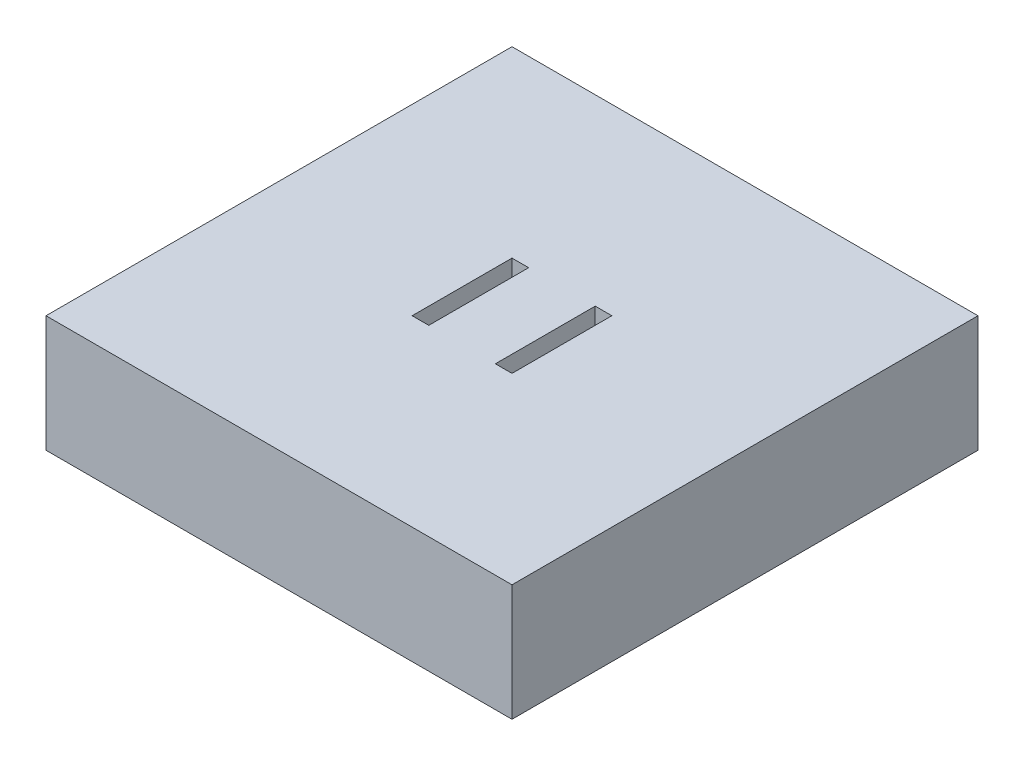
SolidWorks part; units mm, degrees
ref_plane "Front Plane" through (0, 0, 0) normal (0, 0, 1) x (1, 0, 0)
ref_plane "Top Plane" through (0, 0, 0) normal (0, 1, 0) x (1, 0, 0)
ref_plane "Right Plane" through (0, 0, 0) normal (1, 0, 0) x (0, 0, -1)
sketch "Sketch1" plane through (0, 0, 0) normal (0, 1, 0) x (1, 0, 0)
  line L1 (14, -14) -> (-14, -14)
  line L2 (14, -14) -> (14, 14)
  line L3 (14, 14) -> (-14, 14)
  line L4 (-14, -14) -> (-14, 14)
  line L5 (14, -14) -> (-14, 14) construction
  line L6 (14, 14) -> (-14, -14) construction
  circle A0 centre (0, 0) radius 10.625
  point P0 (0, 0)
  dimension "D1" = 21.25
  dimension "D2" = 28
extrude "Boss-Extrude1" add sketch "Sketch1" along normal mid plane 5
sketch "Sketch2" plane through (0, 2.5, 0) normal (0, 1, 0) x (1, 0, 0)
  line L0 (0, 19.8329) -> (0, -19.2543) construction
  line L1 (-20.5694, 0) -> (21.8336, 0) construction
  line L2 (-3, 3) -> (-3, -3)
  line L3 (3, 3) -> (3, -3)
  line L4 (-14, 14) -> (-14, -14)
  line L5 (-14, -14) -> (14, -14)
  line L6 (14, -14) -> (14, 14)
  line L7 (14, 14) -> (-14, 14)
  line L8 (-14, 14) -> (-14, -14)
  line L9 (-14, -14) -> (14, -14)
  line L10 (14, -14) -> (14, 14)
  line L11 (14, 14) -> (-14, 14)
  line L12 (-3, -3) -> (-2, -3)
  line L13 (3, -3) -> (2, -3)
  line L14 (-2, -3) -> (-2, 3)
  line L15 (2, -3) -> (2, 3)
  line L16 (-2, 3) -> (-3, 3)
  line L17 (2, 3) -> (3, 3)
  point P9 (2, 0)
  dimension "D2" = 2
  dimension "D3" = 1
  dimension "D4" = 6
  dimension "D1" = 0
extrude "Boss-Extrude2" add sketch "Sketch2" along normal blind 2
sketch "Sketch3" plane through (0, 0, 0) normal (0, 0, 1) x (1, 0, 0)
  line L0 (-2, 2.5) -> (2, 2.5)
  line L1 (0, 0.9778) -> (0, 2.5) construction
  arc A0 (-2, 2.5) -> (2, 2.5) centre (0, 3.0528) ccw
  dimension "D1" = 2.075
  dimension "D2" = 1.5222
extrude "Boss-Extrude3" add sketch "Sketch3" along normal mid plane 6
chamfer "Chamfer1" distance 1 angle 45 2 edges at (0, 2.5, -3) (0, 2.5, 3)
